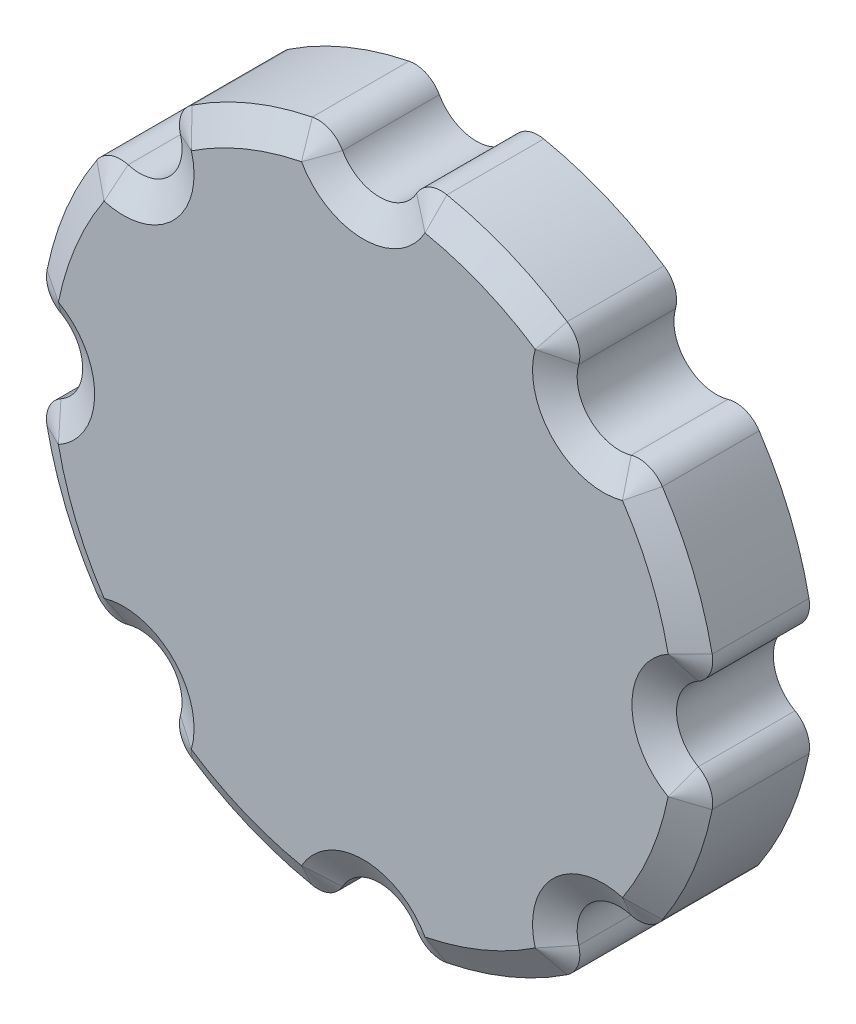
SolidWorks part; units mm, degrees
ref_plane "前视基准面" through (0, 0, 0) normal (0, 0, 1) x (1, 0, 0)
ref_plane "上视基准面" through (0, 0, 0) normal (0, 1, 0) x (1, 0, 0)
ref_plane "右视基准面" through (0, 0, 0) normal (1, 0, 0) x (0, 0, -1)
sketch "草图1" plane through (0, 0, 0) normal (0, 0, 1) x (1, 0, 0)
  circle A0 centre (0, 0) radius 1.5
  circle A1 centre (0, 0) radius 2.75
  dimension "D1" = 3
  dimension "D2" = 5.5
extrude "凸台-拉伸1" add sketch "草图1" along normal blind 1
sketch "草图2" plane through (0, 0, 1) normal (0, 0, 1) x (1, 0, 0)
  circle A0 centre (0, 0) radius 6
  dimension "D1" = 12
extrude "凸台-拉伸2" add sketch "草图2" along normal blind 2
sketch "草图3" plane through (0, 0, 3) normal (0, 0, 1) x (1, 0, 0)
  circle A0 centre (0, 6) radius 0.75
  circle A1 centre (0, 0) radius 6 construction
  circle A2 centre (4.2426, 4.2426) radius 0.75
  circle A3 centre (6, 0) radius 0.75
  circle A4 centre (4.2426, -4.2426) radius 0.75
  circle A5 centre (0, -6) radius 0.75
  circle A6 centre (-4.2426, -4.2426) radius 0.75
  circle A7 centre (-6, 0) radius 0.75
  circle A8 centre (-4.2426, 4.2426) radius 0.75
  point P20 (0, 0)
  dimension "D1" = 1.5
  dimension "D2" = 8
extrude "切除-拉伸1" cut sketch "草图3" against normal blind 22
fillet "圆角1" radius 0.5 16 edges at (3.6802, 4.7388, 2) (4.7388, 3.6802, 2) (5.9531, -0.7485, 2) (5.9531, 0.7485, 2) (4.7388, -3.6802, 2) (3.6802, -4.7388, 2) (-0.7485, -5.9531, 2) (0.7485, -5.9531, 2) (-3.6802, -4.7388, 2) (-4.7388, -3.6802, 2) (-5.9531, -0.7485, 2) (-5.9531, 0.7485, 2) (-4.7388, 3.6802, 2) (-3.6802, 4.7388, 2) (-0.7485, 5.9531, 2) (0.7485, 5.9531, 2)
chamfer "倒角1" distance 0.5 angle 30 32 edges at (4.757, 3.5089, 3) (5.5433, 2.2961, 3) (5.8449, 0.8826, 3) (5.25, 0, 3) (5.8449, -0.8826, 3) (5.5433, -2.2961, 3) (4.757, -3.5089, 3) (3.7123, -3.7123, 3) (3.5089, -4.757, 3) (2.2961, -5.5433, 3) (0.8826, -5.8449, 3) (0, -5.25, 3) (-0.8826, -5.8449, 3) (-2.2961, -5.5433, 3) (-3.5089, -4.757, 3) (-3.7123, -3.7123, 3) (-4.757, -3.5089, 3) (-5.5433, -2.2961, 3) (-5.8449, -0.8826, 3) (-5.25, 0, 3) (-5.8449, 0.8826, 3) (-5.5433, 2.2961, 3) (-4.757, 3.5089, 3) (-3.7123, 3.7123, 3) (-3.5089, 4.757, 3) (-2.2961, 5.5433, 3) (-0.8826, 5.8449, 3) (0, 5.25, 3) (0.8826, 5.8449, 3) (2.2961, 5.5433, 3) (3.5089, 4.757, 3) (3.7123, 3.7123, 3) first distance on face at (0, 0, 3)
